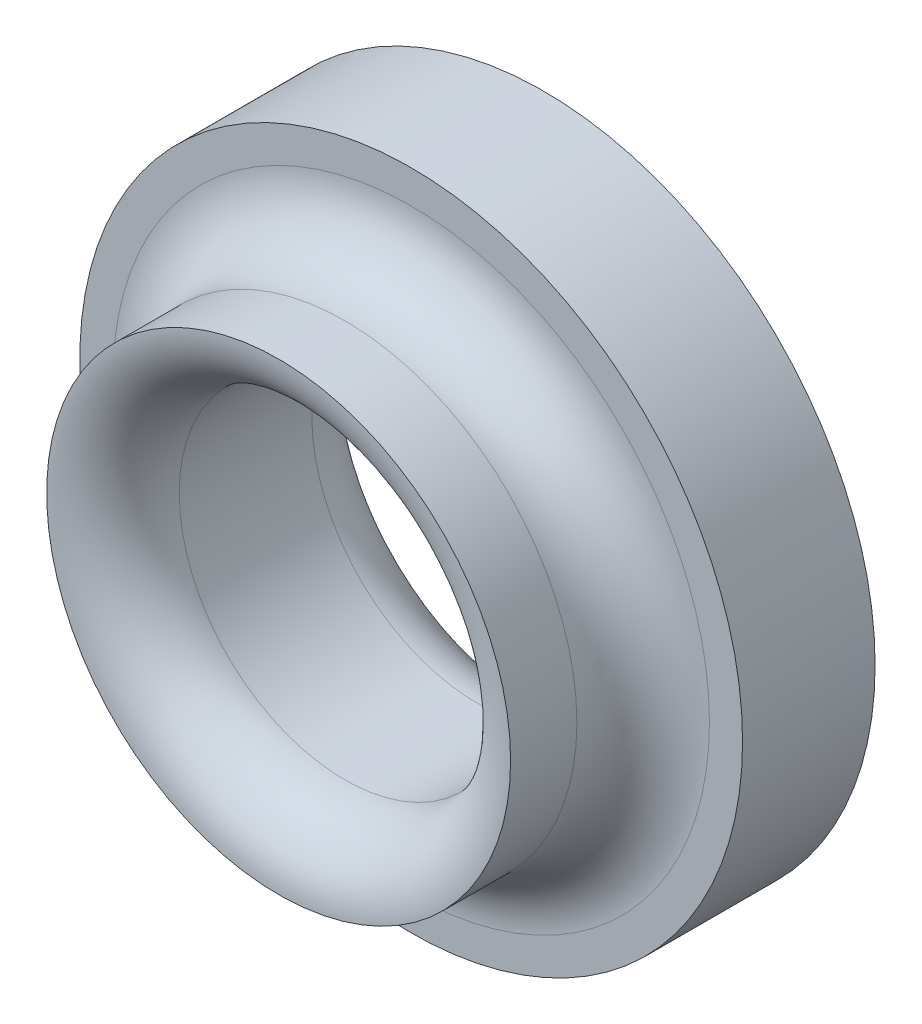
SolidWorks part; units mm, degrees
ref_plane "Front Plane" through (0, 0, 0) normal (0, 0, 1) x (1, 0, 0)
ref_plane "Top Plane" through (0, 0, 0) normal (0, 1, 0) x (1, 0, 0)
ref_plane "Right Plane" through (0, 0, 0) normal (1, 0, 0) x (0, 0, -1)
sketch "Sketch1" plane through (0, 0, 0) normal (0, 0, 1) x (1, 0, 0)
  circle A0 centre (0, 0) radius 5
  dimension "D1" = 10
extrude "Boss-Extrude1" add sketch "Sketch1" along normal blind 2
sketch "Sketch2" plane through (0, 0, 2) normal (0, 0, 1) x (1, 0, 0)
  circle A0 centre (0, 0) radius 2.5
  dimension "D1" = 5
extrude "Cut-Extrude1" cut sketch "Sketch2" against normal blind 10
sketch "Sketch3" plane through (0, 0, 2) normal (0, 0, 1) x (1, 0, 0)
  circle A0 centre (0, 0) radius 3.5
  dimension "D1" = 7
extrude "Boss-Extrude2" add sketch "Sketch3" along normal blind 2
sketch "Sketch4" plane through (0, 0, 2) normal (0, 0, -1) x (-1, 0, 0)
  circle A0 centre (0, 0) radius 2.5
extrude "Cut-Extrude2" cut sketch "Sketch4" against normal blind 3
fillet "Fillet1" radius 1 1 edges at (2.5, 0, 0)
fillet "Fillet2" radius 1 1 edges at (2.5, 0, 4)
fillet "Fillet3" radius 1 1 edges at (3.5, 0, 2)
sketch "Sketch5" plane through (0, 0, 0) normal (0, 0, -1) x (-1, 0, 0)
  circle A0 centre (0, 0) radius 2.5191
